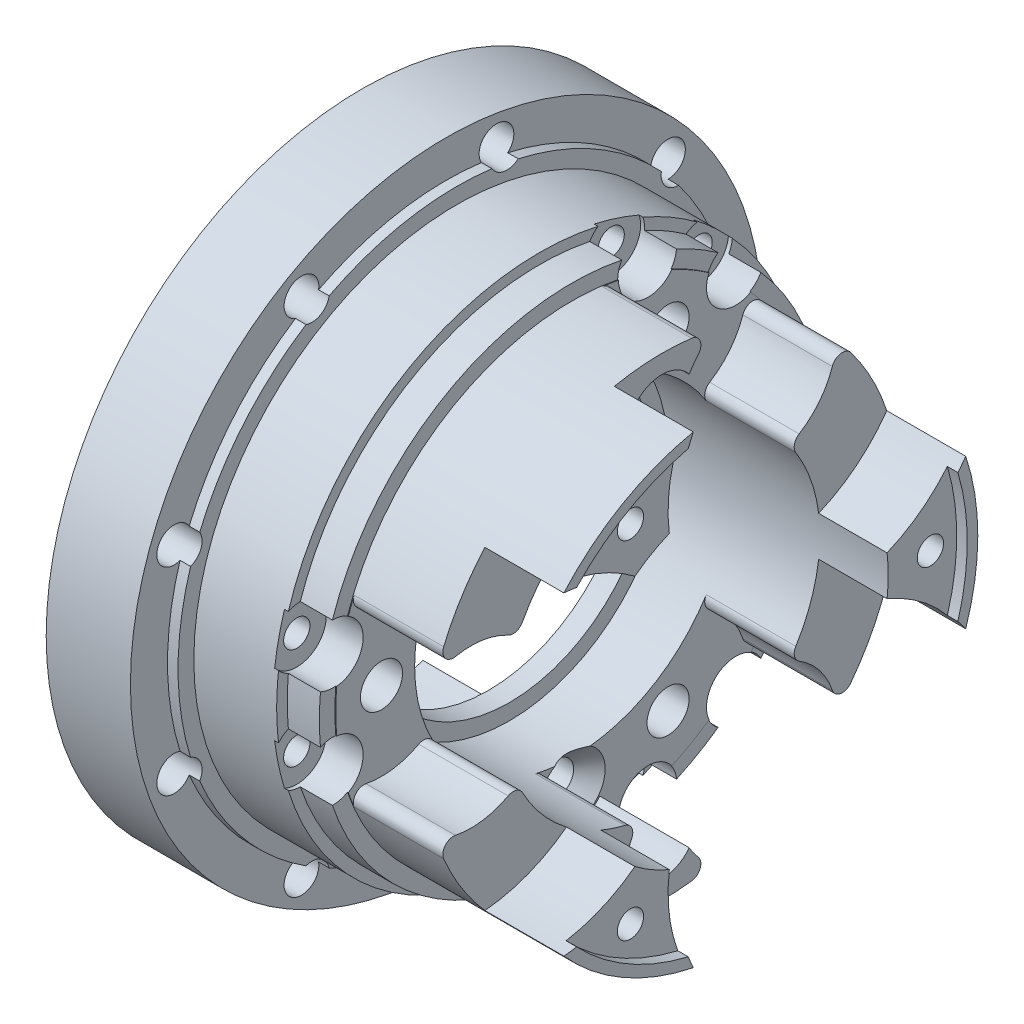
SolidWorks part; units mm, degrees
material "7075-T6 (SN)"
ref_plane "前视基准面" through (0, 0, 0) normal (0, 0, 1) x (1, 0, 0)
ref_plane "上视基准面" through (0, 0, 0) normal (0, 1, 0) x (1, 0, 0)
ref_plane "右视基准面" through (0, 0, 0) normal (1, 0, 0) x (0, 0, -1)
sketch "草图1" plane through (0, 0, 0) normal (0, 0, 1) x (1, 0, 0)
  line L0 (0, 0) -> (35.8207, 0) construction
  line L1 (8, 21.25) -> (12, 21.25)
  line L2 (12, 21.25) -> (12, 13.5)
  line L3 (12, 13.5) -> (14, 13.5)
  line L4 (14, 13.5) -> (14, 15)
  line L5 (14, 15) -> (35, 15)
  line L6 (35, 15) -> (35, 21.5)
  line L7 (35, 21.5) -> (36, 21.5)
  line L8 (36, 21.5) -> (36, 22.5)
  line L9 (36, 22.5) -> (19.92, 22.5)
  line L10 (16.87, 23.525) -> (16.87, 24.975) construction
  line L11 (16.87, 24.975) -> (9, 24.975)
  line L12 (9, 24.975) -> (9, 26.475)
  line L13 (8, 30) -> (0, 30)
  line L14 (0, 30) -> (0, 23)
  line L15 (16.87, 23.525) -> (18.62, 23.525) construction
  line L16 (18.62, 23.525) -> (18.62, 23.975) construction
  line L17 (18.62, 23.975) -> (19.92, 23.975)
  line L18 (19.92, 23.975) -> (19.92, 22.5)
  line L19 (8, 30) -> (8, 26.475)
  line L20 (8, 26.475) -> (9, 26.475)
  line L21 (-1, 22) -> (8, 22)
  line L22 (8, 22) -> (8, 21.25)
  line L23 (0, 23) -> (-1, 23)
  line L24 (-1, 23) -> (-1, 22)
  line L25 (16.87, 24.975) -> (16.87, 23.975)
  line L26 (16.87, 23.975) -> (18.62, 23.975)
  dimension "D1" = 42.5
  dimension "D2" = 49.95
  dimension "D3" = 27
  dimension "D6" = 60
  dimension "D7" = 2
  dimension "D8" = 30
  dimension "D10" = 45
  dimension "D11" = 1
  dimension "D12" = 1
  dimension "D14" = 1.75
  dimension "D15" = 1.3
  dimension "D16" = 23.525
  dimension "D17" = 1
  dimension "D5" = 9
  dimension "D18" = 1
  dimension "D19" = 1.5
  dimension "D4" = 12
  dimension "D20" = 4
  dimension "D21" = 44
  dimension "D22" = 1
  dimension "D23" = 1
  dimension "D13" = 21
  dimension "D9" = 9.62
revolve "旋转1" add sketch "草图1" angle 360 about L0
sketch "草图2" plane through (35, 0, 0) normal (1, 0, 0) x (0, 0, -1)
  line L0 (-18.15, 0) -> (0, 0) construction
  line L1 (0, 0) -> (-9.5, 16.4545) construction
  circle A0 centre (0, 0) radius 18.15 construction
  circle A1 centre (-18.15, 0) radius 2
  circle A2 centre (-9.5, 16.4545) radius 1.25
  dimension "D1" = 36.3
  dimension "D2" = 4
  dimension "D5" = 2.5
  dimension "D3" = 60
  dimension "D4" = 19
extrude "切除-拉伸1" cut sketch "草图2" against normal through all
cosmetic thread "装饰螺纹线1" parameters "D2"=3
sketch "草图4" plane through (36, 0, 0) normal (1, 0, 0) x (0, 0, -1)
  circle A0 centre (-18.15, 0) radius 7.5
  dimension "D1" = 15
extrude "切除-拉伸2" cut sketch "草图4" against normal blind 16
sketch "草图5" plane through (36, 0, 0) normal (1, 0, 0) x (0, 0, -1)
  circle A0 centre (-18.15, 0) radius 15
  dimension "D1" = 30
extrude "切除-拉伸3" cut sketch "草图5" against normal blind 7.5
pattern_circular "阵列(圆周)1" count 3 over 360 about axis through (0, 0, 0) along (1, 0, 0) of "切除-拉伸1", "切除-拉伸3", "切除-拉伸2"
cosmetic thread "装饰螺纹线2" parameters "D2"=3
cosmetic thread "装饰螺纹线3" parameters "D2"=3
sketch "草图6" plane through (12, 0, 0) normal (-1, 0, 0) x (0, 0, 1)
  line L0 (0, 0) -> (-13.5, 0) construction
  line L1 (0, -17.5) -> (17.5, 0) construction
  line L2 (0, -17.5) -> (-17.5, 0) construction
  line L3 (-17.5, 0) -> (0, 17.5) construction
  line L4 (17.5, 0) -> (0, 17.5) construction
  line L5 (0, -17.5) -> (0, 17.5) construction
  line L6 (-17.5, 0) -> (17.5, 0) construction
  circle A1 centre (0, 0) radius 17.5 construction
  circle A2 centre (-17.5, 0) radius 1.6 construction
  circle A3 centre (0, 17.5) radius 1.6
  circle A4 centre (17.5, 0) radius 1.6 construction
  circle A5 centre (0, -17.5) radius 1.6
  circle A6 centre (0, 0) radius 13.5 construction
  point P0 (0, 0)
  dimension "D1" = 35
  dimension "D2" = 3.2
  dimension "D3" = 45
extrude "切除-拉伸4" cut sketch "草图6" against normal through all
sketch "草图7" plane through (28.5, 0, 0) normal (1, 0, 0) x (0, 0, -1)
  circle A0 centre (0, 17.5) radius 3.25
  circle A1 centre (0, -17.5) radius 3.25
  dimension "D1" = 6.5
extrude "切除-拉伸5" cut sketch "草图7" against normal up to surface (8.5 mm away) up to face at (20, 15.7184, -11.075)
chamfer "倒角1" distance 1.5 angle 45 2 edges at (20, 17.5, -1.6) (20, -17.5, -1.6)
sketch "草图8" plane through (-1, 0, 0) normal (-1, 0, 0) x (0, 0, 1)
  line L0 (0, 0) -> (-25.4414, 15.8976)
  line L1 (0, 0) -> (-9.2705, -28.5317)
  line L2 (0, 0) -> (-30, 0) construction
  arc A0 (-25.4414, 15.8976) -> (-9.2705, -28.5317) centre (0, 0) ccw
  circle A1 centre (0, 0) radius 30 construction
  dimension "D1" = 32
  dimension "D2" = 72
extrude "切除-拉伸6" cut sketch "草图8" against normal blind 8
sketch "草图10" plane through (0, 0, 0) normal (-1, 0, 0) x (0, 0, 1)
  line L0 (25.8415, 9.4056) -> (0, 0) construction
  line L1 (0, 0) -> (18.15, 0) construction
  circle A0 centre (0, 0) radius 27.5 construction
  circle A1 centre (25.8415, 9.4056) radius 1.65
  dimension "D1" = 55
  dimension "D2" = 3.3
  dimension "D3" = 20
extrude "切除-拉伸7" cut sketch "草图10" against normal through all
cosmetic thread "装饰螺纹线4" parameters "D2"=4
pattern_circular "阵列(圆周)2" count 9 over 360 about axis through (0, 0, 0) along (1, 0, 0) of "切除-拉伸7"
cosmetic thread "装饰螺纹线5" parameters "D2"=4
cosmetic thread "装饰螺纹线6" parameters "D2"=4
cosmetic thread "装饰螺纹线7" parameters "D2"=4
cosmetic thread "装饰螺纹线8" parameters "D2"=4
cosmetic thread "装饰螺纹线9" parameters "D2"=4
cosmetic thread "装饰螺纹线16" parameters "D2"=4
cosmetic thread "装饰螺纹线17" parameters "D2"=4
fillet "圆角1" radius 1 12 edges at (24.25, 21.9572, -4.9124) (24.25, 15.2329, -16.5593) (24.25, 8.8578, -12.1053) (24.25, -15.2329, -16.5593) (24.25, -21.9572, -4.9124) (24.25, -8.8578, -12.1053) (24.25, -14.8768, 1.9187) (24.25, 6.0546, 13.7238) (24.25, -6.0546, 13.7238) (24.25, -6.7243, 21.4717) (24.25, 6.7243, 21.4717) (24.25, 14.8768, 1.9187)
sketch "草图12" plane through (35, 0, 0) normal (1, 0, 0) x (0, 0, -1)
  line L0 (-23.2, 0) -> (0, 0) construction
  line L1 (0, 0) -> (-22.693, -4.8236) construction
  circle A0 centre (0, 0) radius 23.2 construction
  circle A1 centre (-22.693, -4.8236) radius 3 construction
  circle A2 centre (-22.693, -4.8236) radius 2.8
  circle A3 centre (-22.693, 4.8236) radius 2.8
  dimension "D1" = 46.4
  dimension "D2" = 6
  dimension "D3" = 5.6
  dimension "D4" = 12
extrude "切除-拉伸8" cut sketch "草图12" against normal offset from surface (18.5 mm away) 7.5 up to face at (9, 2.1778, 5.9834)
sketch "草图14" plane through (35, 0, 0) normal (1, 0, 0) x (0, 0, -1)
  circle A0 centre (-22.693, -4.8236) radius 1.25
  circle A1 centre (-22.693, 4.8236) radius 1.25
  dimension "D1" = 2.5
extrude "切除-拉伸9" cut sketch "草图14" against normal blind 8 from surface at -18.5 starting at face at (16.5, -4.717, 22.1917)
cosmetic thread "装饰螺纹线10" parameters "D2"=3
cosmetic thread "装饰螺纹线11" parameters "D2"=3
fillet "圆角2" radius 1 2 edges at (3.5, -28.5317, -9.2705) (3.5, 15.8976, -25.4414)
pattern_circular "阵列(圆周)3" count 3 over 360 about axis through (0, 0, 0) along (1, 0, 0) of "切除-拉伸9", "切除-拉伸8"
cosmetic thread "装饰螺纹线12" parameters "D2"=3
cosmetic thread "装饰螺纹线13" parameters "D2"=3
cosmetic thread "装饰螺纹线14" parameters "D2"=3
cosmetic thread "装饰螺纹线15" parameters "D2"=3
move or copy body "实体-移动/复制1" [suppressed]
equation "\"D9@草图1\"=8+1.57+0.05"
